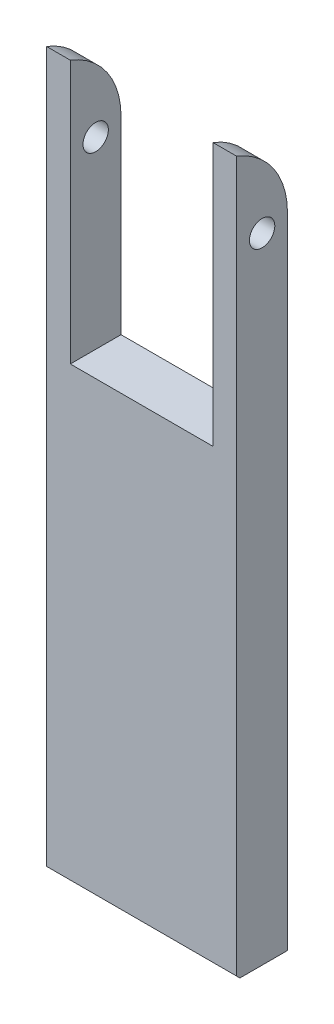
SolidWorks part; units mm, degrees
ref_plane "Front Plane" through (0, 0, 0) normal (0, 0, 1) x (1, 0, 0)
ref_plane "Top Plane" through (0, 0, 0) normal (0, 1, 0) x (1, 0, 0)
ref_plane "Right Plane" through (0, 0, 0) normal (1, 0, 0) x (0, 0, -1)
sketch "Sketch1" plane through (0, 0, 0) normal (0, 0, 1) x (1, 0, 0)
  line L1 (0, 0) -> (60, 0)
  line L2 (0, 0) -> (0, 250)
  line L3 (0, 250) -> (60, 250)
  line L4 (60, 0) -> (60, 250)
extrude "Boss-Extrude1" add sketch "Sketch1" along normal blind 16
chamfer "Chamfer2" distance 1 angle 45 1 edges at (30, 0, 16)
sketch "Sketch2" plane through (0, 0, 0) normal (0, -1, 0) x (-1, 0, 0)
  line L0 (-60, -7.5) -> (0, -7.5) construction
  line L1 (-60, -15) -> (-60, 0) construction
  line L2 (0, -15) -> (0, 0) construction
  line L3 (-30, 0) -> (-30, -16) construction
  line L4 (0, 0) -> (-60, 0) construction
  line L5 (0, -16) -> (-60, -16) construction
  line L6 (-41.5, 0) -> (-41.5, -15)
  line L7 (-18.5, 0) -> (-18.5, -15)
  line L8 (-41.5, 0) -> (-41.5, -16) construction
  line L9 (-60, -15) -> (0, -15) construction
  line L10 (-18.5, 0) -> (-18.5, -16) construction
  circle A0 centre (-41.5, -7.5) radius 2
  circle A1 centre (-18.5, -7.5) radius 2
  dimension "D1" = 11.5
  dimension "D2" = 11.5
extrude "Cut-Extrude1" cut sketch "Sketch2" against normal blind 15 contours A0 | A1
sketch "Sketch3" plane through (0, 0, 0) normal (0, 0, -1) x (-1, 0, 0)
  line L0 (-30, 0) -> (-30, 200) construction
  line L1 (0, 0) -> (-60, 0) construction
  line L3 (-7.5, 175) -> (-52.5, 175)
  line L4 (-7.5, 175) -> (-7.5, 225)
  line L5 (-7.5, 225) -> (-52.5, 225)
  line L6 (-52.5, 175) -> (-52.5, 225)
  line L7 (-7.5, 175) -> (-52.5, 225) construction
  line L8 (-7.5, 225) -> (-52.5, 175) construction
extrude "Cut-Extrude2" cut sketch "Sketch3" against normal through all
sketch "Sketch4" plane through (52.5, 0, 0) normal (-1, 0, 0) x (0, 0, 1)
  line L0 (8, 175) -> (8, 225) construction
  line L1 (16, 175) -> (0, 175) construction
  line L2 (16, 225) -> (0, 225) construction
  circle A0 centre (8, 200) radius 4
extrude "Cut-Extrude3" cut sketch "Sketch4" against normal through all both and the other way through all
sketch "Sketch5" plane through (0, 0, 0) normal (0, 0, -1) x (-1, 0, 0)
  line L0 (0, 250) -> (0, 0) construction
  line L1 (-60, 250) -> (0, 250)
  line L2 (-60, 250) -> (-60, 225)
  line L3 (-60, 225) -> (0, 225)
  line L4 (0, 250) -> (0, 225)
extrude "Cut-Extrude4" cut sketch "Sketch5" against normal through all
sketch "Esboço1" plane through (0, 0, 0) normal (0, 0, -1) x (-1, 0, 0)
  line L1 (-52.5, 175) -> (-7.5, 175)
  line L2 (-52.5, 175) -> (-52.5, 142)
  line L3 (-52.5, 142) -> (-7.5, 142)
  line L4 (-7.5, 175) -> (-7.5, 142)
extrude "Corte-extrusão1" cut sketch "Esboço1" against normal through all
fillet "Filete1" radius 25 2 edges at (56.25, 225, 0) (3.75, 225, 0)
